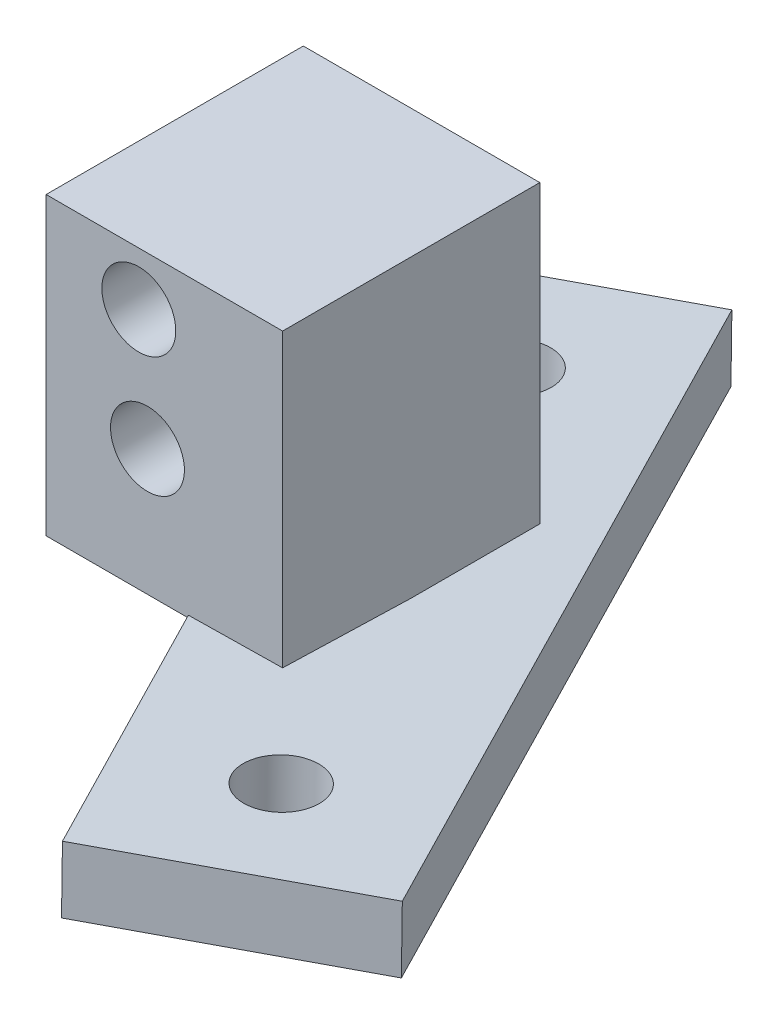
SolidWorks part; units mm, degrees
ref_plane "Front Plane" through (0, 0, 0) normal (0, 0, 1) x (1, 0, 0)
ref_plane "Top Plane" through (0, 0, 0) normal (0, 1, 0) x (1, 0, 0)
ref_plane "Right Plane" through (0, 0, 0) normal (1, 0, 0) x (0, 0, -1)
sketch "Sketch2" plane through (0, 0, 0) normal (0, 0, 1) x (1, 0, 0)
  line L0 (-194.337, 238.2488) -> (-194.337, 212.8488)
  line L1 (-194.337, 212.8488) -> (-174.017, 212.8488)
  line L2 (-174.017, 212.8488) -> (-174.017, 238.2488)
  line L3 (-174.017, 238.2488) -> (-194.337, 238.2488)
  circle A0 centre (-186.3724, 233.6772) radius 3.175
  circle A1 centre (-185.6285, 223.6772) radius 3.175
  dimension "D6" = 6.35
  dimension "D7" = 6.35
  dimension "D1" = 90
  dimension "D2" = 5.08
  dimension "D3" = 20.32
  dimension "D4" = 25.4
  dimension "D5" = 3.175
extrude "Boss-Extrude1" add sketch "Sketch2" along normal up to surface (22.098 mm away)
ref_plane "Plane1" through (-3.3927, 215.0063, -6.5391) normal (-0.0158, 0.9994, -0.0304) x (0.9999, 0.0158, -0.0005)
sketch "Sketch3" plane through (-3.3927, 215.0063, -6.5391) normal (-0.0158, 0.9994, -0.0304) x (0.9999, 0.0158, -0.0005)
  line L0 (-198.6355, 8.8498) -> (-166.4391, -51.7028)
  line L1 (-166.4391, -51.7028) -> (-147.3763, -41.5669)
  line L2 (-147.3763, -41.5669) -> (-179.5727, 18.9857)
  line L3 (-179.5727, 18.9857) -> (-198.6355, 8.8498)
  line L4 (-170.6507, -28.5583) -> (-190.9682, -28.5583) construction
  circle A0 centre (-161.6775, -37.6641) radius 3.175
  circle A1 centre (-184.3342, 4.947) radius 3.175
  dimension "D6" = 10.16
  dimension "D10" = 6.35
  dimension "D11" = 6.35
  dimension "D1" = 21.59
  dimension "D2" = 4.064
  dimension "D3" = 62
  dimension "D4" = 68.58
  dimension "D5" = 26.67
  dimension "D7" = 10.795
  dimension "D8" = 10.16
  dimension "D9" = 10.795
extrude "Boss-Extrude2" add sketch "Sketch3" against normal blind 5.588
